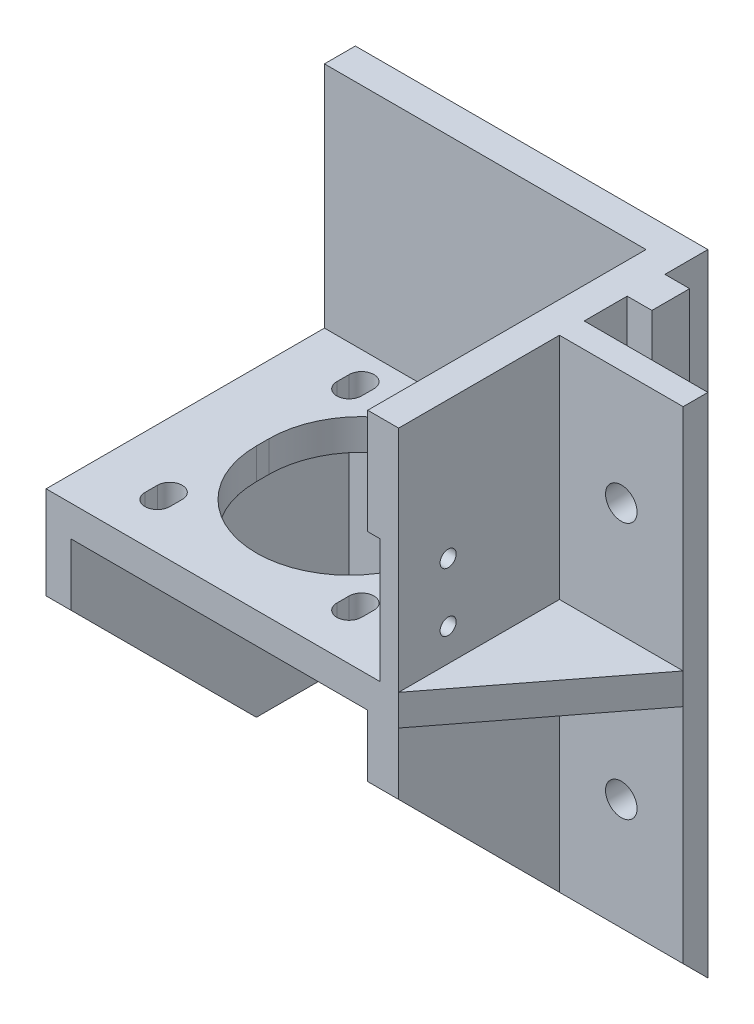
SolidWorks part; units mm, degrees
ref_plane "前视基准面" through (0, 0, 0) normal (0, 0, 1) x (1, 0, 0)
ref_plane "上视基准面" through (0, 0, 0) normal (0, 1, 0) x (1, 0, 0)
ref_plane "右视基准面" through (0, 0, 0) normal (1, 0, 0) x (0, 0, -1)
other "Configuration Table"
sketch "草图1" plane through (0, 0, 0) normal (0, 1, 0) x (1, 0, 0)
  line L6 (-28.5, -25) -> (28.5, -25)
  line L7 (-28.5, -25) -> (-28.5, 25)
  line L8 (-28.5, 25) -> (28.5, 25)
  line L9 (28.5, -25) -> (28.5, 25)
extrude "凸台-拉伸1" add sketch "草图1" along normal blind 5 contours L7 L6 L9 L8
sketch "草图2" plane through (0, 5, 0) normal (0, 1, 0) x (1, 0, 0)
  line L0 (-28.5, 25) -> (28.5, 25) construction
  line L1 (-28.5, -25) -> (-23.5, -25)
  line L2 (-28.5, -25) -> (-28.5, 25)
  line L3 (-28.5, 25) -> (-23.5, 25)
  line L4 (-23.5, -25) -> (-23.5, 25)
  line L6 (28.5, 25) -> (-28.5, 25)
  line L7 (28.5, 25) -> (28.5, 20)
  line L8 (28.5, 20) -> (-28.5, 20)
  line L9 (-28.5, 25) -> (-28.5, 20)
  line M9 (28.5, 25) -> (-28.5, 25)
  line M12 (28.5, -25) -> (28.5, 25)
extrude "凸台-拉伸3" add sketch "草图2" along normal blind 30 contours L8 L4 M12 M9 | L2 L1 L4 L3 region at (2.5, 5, -22.5)
sketch "草图3" plane through (0, 0, 0) normal (0, -1, 0) x (1, 0, 0)
  line L0 (-28.5, 25) -> (28.5, 25) construction
  line L1 (-28.5, -25) -> (-23.5, -25)
  line L2 (-28.5, -25) -> (-28.5, 25)
  line L3 (-28.5, 25) -> (-23.5, 25)
  line L4 (-23.5, -25) -> (-23.5, 25)
  line L5 (28.5, 25) -> (28.5, -25) construction
  line L6 (-28.5, -25) -> (28.5, -25)
  line L7 (-28.5, -25) -> (-28.5, -20)
  line L8 (-28.5, -20) -> (28.5, -20)
  line L9 (28.5, -25) -> (28.5, -20)
  line L11 (28.5, 25) -> (24.5, 25)
  line L12 (28.5, 25) -> (28.5, -25)
  line L13 (28.5, -25) -> (24.5, -25)
  line L14 (24.5, 25) -> (24.5, -25)
  line M10 (-28.5, -25) -> (28.5, -25)
  line M11 (28.5, -25) -> (28.5, 25)
  line M12 (28.5, 25) -> (-28.5, 25)
extrude "凸台-拉伸4" add sketch "草图3" along normal blind 40 contours L14 L8 M12 M11 | L14 L8 L4 M10 | L8 L14 L6 M11 | L2 L1 L4 L3 region at (0.5, 0, -22.5) region at (26.5, 0, -22.5) region at (26.5, 0, 2.5)
sketch "草图5" plane through (28.5, 0, 0) normal (1, 0, 0) x (0, 0, -1)
  line L1 (25, -40) -> (-25, -40) construction
  line L3 (-25, 5) -> (-25, -40) construction
  line L4 (-25, -10) -> (5, -40)
  line L5 (-25, -10) -> (-25, -40)
  line L6 (-25, -40) -> (5, -40)
extrude "切除-拉伸1" cut sketch "草图5" against normal blind 80 contours L4 L6 L5
sketch "草图6" plane through (0, 5, 0) normal (0, 1, 0) x (1, 0, 0)
  line L0 (20.5, -17) -> (20.5, -19)
  line L1 (-23.5, -25) -> (28.5, -25) construction
  line L4 (28.5, 20) -> (-23.5, 20) construction
  line L5 (16.5, -17) -> (16.5, -19)
  line L9 (2.5, -25) -> (2.5, 20)
  line L11 (-15.5, -19) -> (-15.5, -17)
  line L14 (-11.5, -17) -> (-11.5, -19)
  line L15 (16.5, 13) -> (16.5, 11)
  line L16 (-11.5, 13) -> (-11.5, 11)
  line L17 (-15.5, 13) -> (-15.5, 11)
  line L18 (20.5, 13) -> (20.5, 11)
  arc A2 (16.5, -17) -> (20.5, -17) centre (18.5, -17) cw
  arc A3 (16.5, -19) -> (20.5, -19) centre (18.5, -19) ccw
  arc A4 (-15.5, -17) -> (-11.5, -17) centre (-13.5, -17) cw
  arc A5 (-15.5, -19) -> (-11.5, -19) centre (-13.5, -19) ccw
  circle A6 centre (2.5, -1) radius 15
  arc A7 (-15.5, 11) -> (-11.5, 11) centre (-13.5, 11) ccw
  arc A8 (-15.5, 13) -> (-11.5, 13) centre (-13.5, 13) cw
  arc A9 (16.5, 11) -> (20.5, 11) centre (18.5, 11) ccw
  arc A10 (16.5, 13) -> (20.5, 13) centre (18.5, 13) cw
extrude "切除-拉伸2" cut sketch "草图6" against normal blind 80 contours L9 A6 | L9 A6 | A8 L17 A7 L16 | L11 A5 L14 A4 | L5 A3 L0 A2 | A10 L15 A9 L18 | A6 region at (18.5, 5, 18) region at (-3.8662, 5, 1) region at (8.8662, 5, 1) region at (-13.5, 5, 18) region at (18.5, 5, -12) region at (-13.5, 5, -12)
sketch "草图7" plane through (0, 0, -20) normal (0, 0, 1) x (1, 0, 0)
  line L0 (-23.5, 5) -> (-11.5, 5)
  line L1 (28.5, 5) -> (-23.5, 5) construction
  line L2 (-11.5, 5) -> (-11.5, 21)
  line L3 (-11.5, 21) -> (-15.5, 21)
  line L4 (-15.5, 21) -> (-15.5, 17)
  circle A4 centre (-15.5, 17) radius 3
extrude "切除-拉伸6" cut sketch "草图7" against normal blind 80 contours A4
sketch "草图8" plane through (-28.5, 0, 0) normal (-1, 0, 0) x (0, 0, 1)
  line L0 (-18.05, 35) -> (-11.95, 35)
  line L1 (25, 35) -> (-25, 35) construction
  line L2 (-5, 35) -> (-5, 15)
  line L3 (-18.05, -40) -> (-11.95, -40)
  line L7 (-25, -40) -> (-5, -40) construction
  line L8 (-18.05, -40) -> (-18.05, 35)
  line L10 (-11.95, 35) -> (-11.95, -40)
extrude "凸台-拉伸5" add sketch "草图8" along normal blind 4 contours L3 L10 L0 L8
sketch "草图9" plane through (-28.5, 0, 0) normal (-1, 0, 0) x (0, 0, 1)
  line L0 (-5, -40) -> (-5, 35)
  line L2 (25, 35) -> (-11.95, 35) construction
  line L3 (-5, 35) -> (-1, 35)
  line L4 (-1, 35) -> (-1, -36)
  line L5 (-5, -40) -> (25, -10) construction
  line L6 (-1, -36) -> (-5, -40)
extrude "凸台-拉伸6" add sketch "草图9" along normal blind 20 contours L6 L0 L3 L4
sketch "草图10" plane through (0, 0, -1) normal (0, 0, 1) x (1, 0, 0)
  line L1 (-48.5, 35) -> (-48.5, -36) construction
  line L2 (-48.5, 5) -> (-48.5, 0)
  line L3 (-48.5, 0) -> (-28.5, 0)
  line L4 (-28.5, 35) -> (-28.5, -10) construction
  line L5 (-28.5, 0) -> (-28.5, 5)
  line L6 (-28.5, 5) -> (-48.5, 5)
extrude "凸台-拉伸7" add sketch "草图10" along normal blind 26 contours L2 L3 L5 L6
sketch "草图11" plane through (0, 0, 0) normal (0, -1, 0) x (1, 0, 0)
  line L0 (-48.5, 25) -> (-48.5, -1)
  line L1 (-48.5, -1) -> (-28.5, 25)
  line L2 (-28.5, 25) -> (-48.5, 25)
extrude "切除-拉伸7" cut sketch "草图11" against normal blind 26 contours L2 L0 L1
sketch "草图14" plane through (0, 35, 0) normal (0, 1, 0) x (1, 0, 0)
  line L1 (-28.5, 25) -> (28.5, 25)
  line L2 (-28.5, 25) -> (-28.5, 20)
  line L3 (-28.5, 20) -> (28.5, 20)
  line L4 (28.5, 25) -> (28.5, 20)
  line L5 (-23.5, -25) -> (-28.5, -25)
  line L6 (-23.5, -25) -> (-23.5, 20)
  line L7 (-23.5, 20) -> (-28.5, 20)
  line L8 (-28.5, -25) -> (-28.5, 20)
  line L9 (-48.5, 5) -> (-28.5, 5)
  line L10 (-48.5, 5) -> (-48.5, 1)
  line L11 (-48.5, 1) -> (-28.5, 1)
  line L12 (-28.5, 5) -> (-28.5, 1)
  line L13 (-32.5, 11.95) -> (-28.5, 11.95)
  line L14 (-32.5, 11.95) -> (-32.5, 18.05)
  line L15 (-32.5, 18.05) -> (-28.5, 18.05)
  line L16 (-28.5, 11.95) -> (-28.5, 18.05)
  line M8 (-28.5, 25) -> (-28.5, 18.05)
  line M9 (-28.5, 18.05) -> (-32.5, 18.05)
  line M10 (-32.5, 18.05) -> (-32.5, 11.95)
  line M11 (-32.5, 11.95) -> (-28.5, 11.95)
  line M12 (-28.5, 11.95) -> (-28.5, 5)
  line M13 (-28.5, 5) -> (-48.5, 5)
  line M14 (-48.5, 5) -> (-48.5, 1)
  line M15 (-48.5, 1) -> (-28.5, 1)
  line M16 (-28.5, 1) -> (-28.5, -25)
  line M17 (-28.5, -25) -> (-23.5, -25)
  line M18 (-23.5, -25) -> (-23.5, 20)
extrude "凸台-拉伸8" add sketch "草图14" along normal blind 7 contours L8 L3 M16 M17 M18 M8 M12 | L8 M11 M9 M10 | L8 M15 M13 M14 | L2 L1 L4 L3 region at (-26, 35, 2.5) region at (-30.5, 35, -15) region at (-38.5, 35, -3)
sketch "草图15" plane through (0, 0, -1) normal (0, 0, 1) x (1, 0, 0)
  line L0 (-48.5, 42) -> (-28.5, 5)
  line L1 (-48.5, 0) -> (-28.5, -36)
  circle A0 centre (-38.5, 23.5) radius 2.55
  circle A1 centre (-38.5, -18) radius 2.55
extrude "切除-拉伸9" cut sketch "草图15" against normal blind 7 contours L0 A0 | L0 A0 | L1 A1 | L1 A1 region at (-37.5479, 24.0146, -1) region at (-39.4521, 22.9854, -1) region at (-37.5539, -17.4744, -1) region at (-39.4461, -18.5256, -1)
sketch "草图16" plane through (0, 5, 0) normal (0, 1, 0) x (1, 0, 0)
  line L1 (-16.5233, 16.4764) -> (-10.9881, 16.4764)
  line L2 (-16.5233, 16.4764) -> (-16.5233, 8.6568)
  line L3 (-16.5233, 8.6568) -> (-10.9881, 8.6568)
  line L4 (-10.9881, 16.4764) -> (-10.9881, 8.6568)
  line L5 (-16.9626, -13.44) -> (-10.9881, -13.44)
  line L6 (-16.9626, -13.44) -> (-16.9626, -21.5671)
  line L7 (-16.9626, -21.5671) -> (-10.9881, -21.5671)
  line L8 (-10.9881, -13.44) -> (-10.9881, -21.5671)
  line L9 (15.0625, -13.44) -> (22.7063, -13.44)
  line L10 (15.0625, -13.44) -> (15.0625, -21.9625)
  line L11 (15.0625, -21.9625) -> (22.7063, -21.9625)
  line L12 (22.7063, -13.44) -> (22.7063, -21.9625)
  line L13 (15.0625, 16.74) -> (22.4428, 16.74)
  line L14 (15.0625, 16.74) -> (15.0625, 8.6568)
  line L15 (15.0625, 8.6568) -> (22.4428, 8.6568)
  line L16 (22.4428, 16.74) -> (22.4428, 8.6568)
extrude "凸台-拉伸9" add sketch "草图16" against normal blind 5
sketch "草图17" plane through (0, 5, 0) normal (0, 1, 0) x (1, 0, 0)
  line L9 (17, 15.5) -> (17, 13.5)
  line L10 (-14, 15.5) -> (-14, 13.5)
  line L11 (-12, 13.5) -> (-12, 15.5)
  line L12 (19, 15.5) -> (19, 13.5)
  line L14 (17, -15.5) -> (17, -17.5)
  line L15 (19, -15.5) -> (19, -17.5)
  line L19 (-14, -15.5) -> (-14, -17.5)
  line L20 (-12, -15.5) -> (-12, -17.5)
  arc A1 (-14, 15.5) -> (-12, 15.5) centre (-13, 15.5) cw
  arc A2 (-14, 13.5) -> (-12, 13.5) centre (-13, 13.5) ccw
  arc A3 (19, 15.5) -> (17, 15.5) centre (18, 15.5) ccw
  arc A4 (19, 13.5) -> (17, 13.5) centre (18, 13.5) cw
  arc A5 (19, -15.5) -> (17, -15.5) centre (18, -15.5) ccw
  arc A6 (19, -17.5) -> (17, -17.5) centre (18, -17.5) cw
  arc A7 (-14, -15.5) -> (-12, -15.5) centre (-13, -15.5) cw
  arc A8 (-14, -17.5) -> (-12, -17.5) centre (-13, -17.5) ccw
extrude "切除-拉伸10" cut sketch "草图17" against normal blind 5 contours A2 L11 A1 L10 | A8 L20 A7 L19 | A6 L14 A5 L15 | A4 L9 A3 L12
sketch "草图18" plane through (0, 5, 0) normal (0, 1, 0) x (1, 0, 0)
  line L3 (-12.5, -1) -> (-12.5, 0)
  line L4 (-12.5, -1) -> (-12.5, -2)
  line L5 (17.5, -1) -> (17.5, 0)
  line L6 (17.5, -1) -> (17.5, -2)
  circle A1 centre (2.5, -1) radius 15 construction
  arc A2 (-12.5, 0) -> (17.5, 0) centre (2.5, 0) cw
  arc A3 (-12.5, -2) -> (17.5, -2) centre (2.5, -2) ccw
extrude "切除-拉伸11" cut sketch "草图18" against normal blind 5
sketch "草图19" plane through (0, 0, -25) normal (0, 0, -1) x (-1, 0, 0)
  circle A0 centre (15.5, 17) radius 3.05
extrude "切除-拉伸12" cut sketch "草图19" against normal blind 10
mirror "镜向3" about plane through (28.5, 5, 25) normal (-1, 0, 0) of "凸台-拉伸4", "凸台-拉伸5", "凸台-拉伸8", "切除-拉伸1", "切除-拉伸7", "凸台-拉伸7", "切除-拉伸9", "凸台-拉伸6", "切除-拉伸12", "切除-拉伸10", "切除-拉伸11", "凸台-拉伸1", "凸台-拉伸3"
sketch "草图21" plane through (0, 0, -1) normal (0, 0, 1) x (1, 0, 0)
  line L0 (-23.5, 42) -> (80.5, 42) construction
  line L1 (-48.5, -40) -> (28.5, -40)
  line L2 (-48.5, -40) -> (-48.5, 42)
  line L3 (-48.5, 42) -> (28.5, 42)
  line L4 (28.5, -40) -> (28.5, 42)
extrude "切除-拉伸13" cut sketch "草图21" against normal blind 50
sketch "草图22" plane through (0, 0, -1) normal (0, 0, -1) x (-1, 0, 0)
  line L1 (-28.5, -36) -> (52.1244, -36)
  line L2 (-28.5, -36) -> (-28.5, 42)
  line L3 (-28.5, 42) -> (52.1244, 42)
  line L4 (52.1244, -36) -> (52.1244, 42)
extrude "切除-拉伸14" cut sketch "草图22" against normal blind 50
sketch "草图23" plane through (0, 5, 0) normal (0, 1, 0) x (1, 0, 0)
  line L1 (41, 15.5) -> (41, 13.5)
  line L2 (37, 15.5) -> (37, 13.5)
  line L3 (68, 15.5) -> (68, 13.5)
  line L4 (72, 15.5) -> (72, 13.5)
  line L5 (41, -15.5) -> (41, -17.5)
  line L6 (37, -15.5) -> (37, -17.5)
  line L7 (72, -15.5) -> (72, -17.5)
  line L8 (68, -15.5) -> (68, -17.5)
  arc A0 (41, 15.5) -> (37, 15.5) centre (39, 15.5) ccw
  arc A1 (41, 13.5) -> (37, 13.5) centre (39, 13.5) cw
  arc A2 (68, 15.5) -> (72, 15.5) centre (70, 15.5) cw
  arc A3 (68, 13.5) -> (72, 13.5) centre (70, 13.5) ccw
  arc A4 (41, -15.5) -> (37, -15.5) centre (39, -15.5) ccw
  arc A5 (41, -17.5) -> (37, -17.5) centre (39, -17.5) cw
  arc A6 (72, -15.5) -> (68, -15.5) centre (70, -15.5) ccw
  arc A7 (72, -17.5) -> (68, -17.5) centre (70, -17.5) cw
extrude "切除-拉伸15" cut sketch "草图23" against normal blind 10 contours A0 L2 A1 L1 | A2 L4 A3 L3 | A6 L8 A7 L7 | A4 L6 A5 L5
sketch "草图24" plane through (0, 0, 25) normal (0, 0, 1) x (1, 0, 0)
  line L1 (80.5, 5) -> (82.5, 5)
  line L2 (80.5, 5) -> (80.5, 25)
  line L3 (80.5, 25) -> (82.5, 25)
  line L4 (82.5, 5) -> (82.5, 25)
extrude "切除-拉伸16" cut sketch "草图24" against normal blind 15
sketch "草图25" plane through (82.5, 0, 0) normal (-1, 0, 0) x (0, 0, 1)
  line L0 (25, 25) -> (25, 5)
  line L1 (25, 15) -> (17, 15)
  line L2 (17, 15) -> (17, 19.75)
  line L4 (17, 15) -> (17, 10.25)
  circle A0 centre (17, 19.75) radius 1.3
  circle A1 centre (17, 10.25) radius 1.3
extrude "切除-拉伸17" cut sketch "草图25" against normal blind 15 contours A0 | A1 region at (82.5, 20.6432, 16.1068) region at (82.5, 11.1432, 17.8932)
